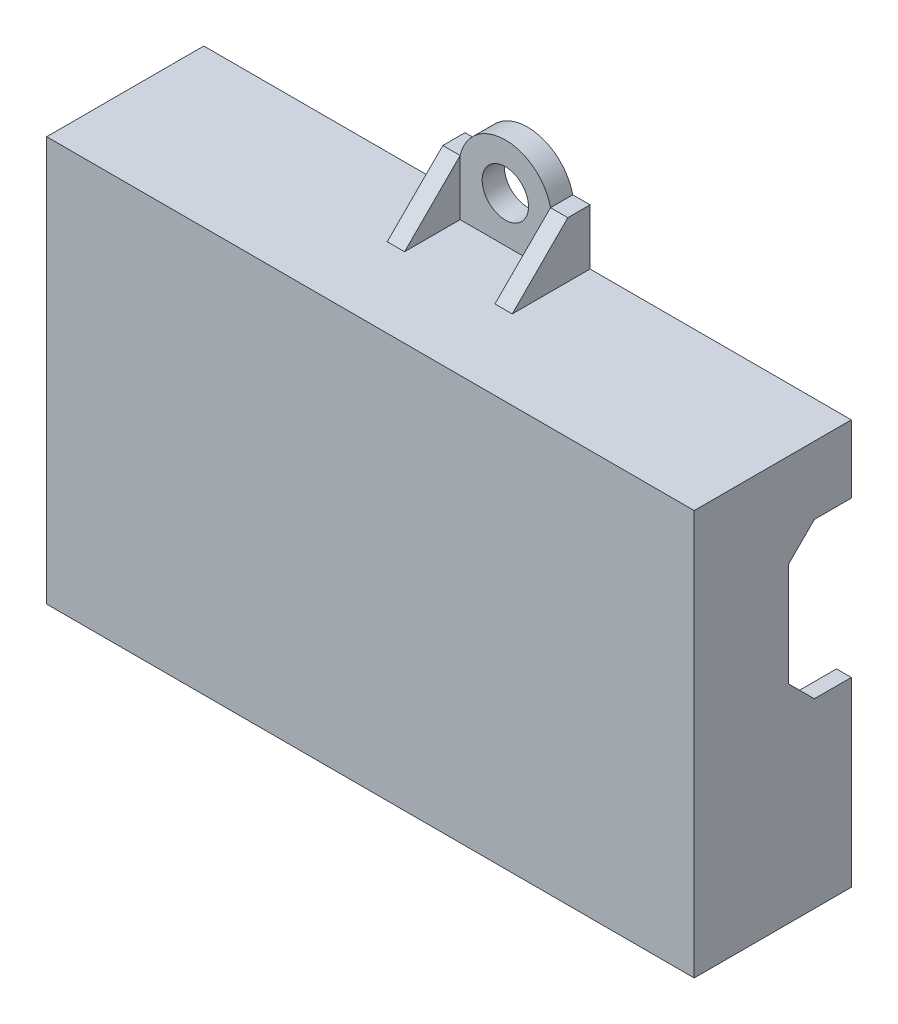
SolidWorks part; units mm, degrees
ref_plane "Front Plane" through (0, 0, 0) normal (0, 0, 1) x (1, 0, 0)
ref_plane "Top Plane" through (0, 0, 0) normal (0, 1, 0) x (1, 0, 0)
ref_plane "Right Plane" through (0, 0, 0) normal (1, 0, 0) x (0, 0, -1)
sketch "Sketch1" plane through (0, 0, 0) normal (0, 0, 1) x (1, 0, 0)
  line L0 (-16.375, 9.825) -> (16.375, -9.825) construction
  line L1 (-16.375, -9.825) -> (-16.675, -9.825) construction
  line L2 (16.675, 10.125) -> (-16.675, 10.125)
  line L3 (16.675, 10.125) -> (16.675, -10.125)
  line L4 (-16.375, 9.825) -> (-16.375, -9.825)
  line L5 (-16.375, -9.825) -> (16.375, -9.825)
  line L6 (16.375, -9.825) -> (16.375, 9.825)
  line L7 (16.375, 9.825) -> (-16.375, 9.825)
  line L8 (-16.375, 9.825) -> (-16.375, -9.825)
  line L9 (-16.375, -9.825) -> (16.375, -9.825)
  line L10 (16.375, -9.825) -> (16.375, 9.825)
  line L11 (16.375, 9.825) -> (-16.375, 9.825)
  line L12 (16.675, -10.125) -> (-16.675, -10.125)
  line L13 (-16.675, 10.125) -> (-16.675, -10.125)
  line L14 (16.675, 10.125) -> (-16.675, -10.125) construction
  line L15 (-13.9701, -11.875) -> (-3.4641, -11.875)
  line L18 (3.4641, -11.875) -> (13.9701, -11.875)
  line L19 (14.8161, -12.3418) -> (24.6724, -27.981)
  line L20 (31.4404, -23.7156) -> (19.404, -4.6171)
  line L21 (19.25, -4.084) -> (19.25, 4.084)
  line L22 (19.404, 4.6171) -> (31.4404, 23.7156)
  line L23 (24.6724, 27.981) -> (14.8161, 12.3418)
  line L24 (13.9701, 11.875) -> (3.4641, 11.875)
  line L25 (-3.4641, 11.875) -> (-13.9701, 11.875)
  line L26 (-14.8161, 12.3418) -> (-24.6724, 27.981)
  line L27 (-31.4404, 23.7156) -> (-19.404, 4.6171)
  line L28 (-19.25, 4.084) -> (-19.25, 3.4641)
  line L29 (-19.25, -3.4641) -> (-19.25, -4.084)
  line L30 (-19.404, -4.6171) -> (-31.4404, -23.7156)
  line L31 (-24.6724, -27.981) -> (-14.8161, -12.3418)
  line L32 (-13.9701, -11.875) -> (-3.4641, -11.875)
  line L33 (3.4641, -11.875) -> (13.9701, -11.875)
  line L34 (14.8161, -12.3418) -> (24.6724, -27.981)
  line L35 (31.4404, -23.7156) -> (19.404, -4.6171)
  line L36 (19.25, -4.084) -> (19.25, 4.084)
  line L37 (19.404, 4.6171) -> (31.4404, 23.7156)
  line L38 (24.6724, 27.981) -> (14.8161, 12.3418)
  line L39 (13.9701, 11.875) -> (3.4641, 11.875)
  line L40 (-3.4641, 11.875) -> (-13.9701, 11.875)
  line L41 (-14.8161, 12.3418) -> (-24.6724, 27.981)
  line L42 (-31.4404, 23.7156) -> (-19.404, 4.6171)
  line L43 (-19.25, 4.084) -> (-19.25, 3.4641)
  line L44 (-19.25, -3.4641) -> (-19.25, -4.084)
  line L45 (-19.404, -4.6171) -> (-31.4404, -23.7156)
  line L46 (-24.6724, -27.981) -> (-14.8161, -12.3418)
  line L47 (16.675, -10.125) -> (-16.675, 10.125) construction
  line L48 (-16.375, -9.825) -> (-16.375, -10.125) construction
  line L49 (-16.675, -10.125) -> (-17.475, -10.125) construction
  line L50 (17.475, 10.925) -> (-17.475, 10.925)
  line L51 (17.475, 10.925) -> (17.475, -10.925)
  line L52 (17.475, -10.925) -> (-17.475, -10.925)
  line L53 (-17.475, 10.925) -> (-17.475, -10.925)
  line L54 (17.475, 10.925) -> (-17.475, -10.925) construction
  line L55 (17.475, -10.925) -> (-17.475, 10.925) construction
  line L56 (-16.675, -10.125) -> (-16.675, -10.925) construction
  line L57 (-20.3929, -2.4744) -> (-17.475, -2.4744)
  line L58 (-20.3929, 2.4744) -> (-17.475, 2.4744)
  line L59 (-2.4744, -13.0179) -> (-2.4744, -10.925)
  line L60 (2.4744, -13.0179) -> (2.4744, -10.925)
  line L61 (-2.4744, 13.0179) -> (-2.4744, 10.925)
  line L62 (2.4744, 13.0179) -> (2.4744, 10.925)
  circle A0 centre (0, -13.375) radius 1.25
  circle A1 centre (-20.75, 0) radius 1.25
  circle A2 centre (0, 13.375) radius 1.25
  arc A32 (-2.4744, -13.0179) -> (-3.4641, -11.875) centre (-3.4641, -12.875) ccw
  arc A33 (-2.4744, -13.0179) -> (2.4744, -13.0179) centre (0, -13.375) ccw
  arc A34 (3.4641, -11.875) -> (2.4744, -13.0179) centre (3.4641, -12.875) ccw
  arc A35 (14.8161, -12.3418) -> (13.9701, -11.875) centre (13.9701, -12.875) ccw
  arc A36 (24.7505, -28.8963) -> (24.6724, -27.981) centre (23.8264, -28.5142) ccw
  arc A37 (24.7505, -28.8963) -> (32.2325, -24.1809) centre (31.8198, -31.8198) ccw
  arc A38 (31.4404, -23.7156) -> (32.2325, -24.1809) centre (32.2864, -23.1824) ccw
  arc A39 (19.25, -4.084) -> (19.404, -4.6171) centre (20.25, -4.084) ccw
  arc A40 (19.404, 4.6171) -> (19.25, 4.084) centre (20.25, 4.084) ccw
  arc A41 (32.2325, 24.1809) -> (31.4404, 23.7156) centre (32.2864, 23.1824) ccw
  arc A42 (32.2325, 24.1809) -> (24.7505, 28.8963) centre (31.8198, 31.8198) ccw
  arc A43 (24.6724, 27.981) -> (24.7505, 28.8963) centre (23.8264, 28.5142) ccw
  arc A44 (13.9701, 11.875) -> (14.8161, 12.3418) centre (13.9701, 12.875) ccw
  arc A45 (2.4744, 13.0179) -> (3.4641, 11.875) centre (3.4641, 12.875) ccw
  arc A46 (2.4744, 13.0179) -> (-2.4744, 13.0179) centre (0, 13.375) ccw
  arc A47 (-3.4641, 11.875) -> (-2.4744, 13.0179) centre (-3.4641, 12.875) ccw
  arc A48 (-14.8161, 12.3418) -> (-13.9701, 11.875) centre (-13.9701, 12.875) ccw
  arc A49 (-24.7505, 28.8963) -> (-24.6724, 27.981) centre (-23.8264, 28.5142) ccw
  arc A50 (-24.7505, 28.8963) -> (-32.2325, 24.1809) centre (-31.8198, 31.8198) ccw
  arc A51 (-31.4404, 23.7156) -> (-32.2325, 24.1809) centre (-32.2864, 23.1824) ccw
  arc A52 (-19.25, 4.084) -> (-19.404, 4.6171) centre (-20.25, 4.084) ccw
  arc A53 (-20.3929, 2.4744) -> (-19.25, 3.4641) centre (-20.25, 3.4641) ccw
  arc A54 (-20.3929, 2.4744) -> (-20.3929, -2.4744) centre (-20.75, 0) ccw
  arc A55 (-19.25, -3.4641) -> (-20.3929, -2.4744) centre (-20.25, -3.4641) ccw
  arc A56 (-19.404, -4.6171) -> (-19.25, -4.084) centre (-20.25, -4.084) ccw
  arc A57 (-32.2325, -24.1809) -> (-31.4404, -23.7156) centre (-32.2864, -23.1824) ccw
  arc A58 (-32.2325, -24.1809) -> (-24.7505, -28.8963) centre (-31.8198, -31.8198) ccw
  arc A59 (-24.6724, -27.981) -> (-24.7505, -28.8963) centre (-23.8264, -28.5142) ccw
  arc A60 (-13.9701, -11.875) -> (-14.8161, -12.3418) centre (-13.9701, -12.875) ccw
  arc A61 (-2.4744, -13.0179) -> (-3.4641, -11.875) centre (-3.4641, -12.875) ccw
  arc A62 (-2.4744, -13.0179) -> (2.4744, -13.0179) centre (0, -13.375) ccw
  arc A63 (3.4641, -11.875) -> (2.4744, -13.0179) centre (3.4641, -12.875) ccw
  arc A64 (14.8161, -12.3418) -> (13.9701, -11.875) centre (13.9701, -12.875) ccw
  arc A65 (24.7505, -28.8963) -> (24.6724, -27.981) centre (23.8264, -28.5142) ccw
  arc A66 (24.7505, -28.8963) -> (32.2325, -24.1809) centre (31.8198, -31.8198) ccw
  arc A67 (31.4404, -23.7156) -> (32.2325, -24.1809) centre (32.2864, -23.1824) ccw
  arc A68 (19.25, -4.084) -> (19.404, -4.6171) centre (20.25, -4.084) ccw
  arc A69 (19.404, 4.6171) -> (19.25, 4.084) centre (20.25, 4.084) ccw
  arc A70 (32.2325, 24.1809) -> (31.4404, 23.7156) centre (32.2864, 23.1824) ccw
  arc A71 (32.2325, 24.1809) -> (24.7505, 28.8963) centre (31.8198, 31.8198) ccw
  arc A72 (24.6724, 27.981) -> (24.7505, 28.8963) centre (23.8264, 28.5142) ccw
  arc A73 (13.9701, 11.875) -> (14.8161, 12.3418) centre (13.9701, 12.875) ccw
  arc A74 (2.4744, 13.0179) -> (3.4641, 11.875) centre (3.4641, 12.875) ccw
  arc A75 (2.4744, 13.0179) -> (-2.4744, 13.0179) centre (0, 13.375) ccw
  arc A76 (-3.4641, 11.875) -> (-2.4744, 13.0179) centre (-3.4641, 12.875) ccw
  arc A77 (-14.8161, 12.3418) -> (-13.9701, 11.875) centre (-13.9701, 12.875) ccw
  arc A78 (-24.7505, 28.8963) -> (-24.6724, 27.981) centre (-23.8264, 28.5142) ccw
  arc A79 (-24.7505, 28.8963) -> (-32.2325, 24.1809) centre (-31.8198, 31.8198) ccw
  arc A80 (-31.4404, 23.7156) -> (-32.2325, 24.1809) centre (-32.2864, 23.1824) ccw
  arc A81 (-19.25, 4.084) -> (-19.404, 4.6171) centre (-20.25, 4.084) ccw
  arc A82 (-20.3929, 2.4744) -> (-19.25, 3.4641) centre (-20.25, 3.4641) ccw
  arc A83 (-20.3929, 2.4744) -> (-20.3929, -2.4744) centre (-20.75, 0) ccw
  arc A84 (-19.25, -3.4641) -> (-20.3929, -2.4744) centre (-20.25, -3.4641) ccw
  arc A85 (-19.404, -4.6171) -> (-19.25, -4.084) centre (-20.25, -4.084) ccw
  arc A86 (-32.2325, -24.1809) -> (-31.4404, -23.7156) centre (-32.2864, -23.1824) ccw
  arc A87 (-32.2325, -24.1809) -> (-24.7505, -28.8963) centre (-31.8198, -31.8198) ccw
  arc A88 (-24.6724, -27.981) -> (-24.7505, -28.8963) centre (-23.8264, -28.5142) ccw
  arc A89 (-13.9701, -11.875) -> (-14.8161, -12.3418) centre (-13.9701, -12.875) ccw
  point P6 (0, 0)
  point P25 (0, 0)
  dimension "D4" = 0.8
  dimension "D5" = 2.5
  dimension "D1" = 0
  dimension "D2" = 0
  dimension "D3" = 0.3
extrude "Boss-Extrude1" add sketch "Sketch1" along normal offset from surface (7.98 mm away) 2.5 contours A84 L57 L53 L58 A82 A83 | L50 L53 L52 L51 L13 L2 L3 L12 | A63 L60 L52 L59 A61 A62 | A76 L61 L50 L62 A74 A75 region at (-2.404, -11.8286, 0) region at (-9.9747, -10.5128, 0) region at (-18.7911, -2.398, 0) region at (0, 10.9954, 0) offset beyond the face yes
sketch "Sketch2" plane through (0, 0, 7.98) normal (0, 0, 1) x (1, 0, 0)
  line L0 (-2.5, 10.925) -> (2.4744, 10.925)
  line L1 (-17.475, 2.4744) -> (-17.475, -2.5)
  line L2 (-2.5, -10.925) -> (2.4744, -10.925)
  line L6 (-20.1071, -2.4744) -> (-17.475, -2.4744)
  line L7 (-20.1071, -2.4744) -> (-17.475, -2.4744)
  line L8 (-17.475, -2.4744) -> (-17.475, -10.925)
  line L9 (-17.475, -2.4744) -> (-17.475, -10.925)
  line L20 (-17.475, -10.925) -> (-2.4744, -10.925)
  line L21 (-17.475, -10.925) -> (-2.4744, -10.925)
  line L22 (-2.4744, -10.925) -> (-2.4744, -12.7321)
  line L23 (-2.4744, -10.925) -> (-2.4744, -12.7321)
  line L24 (2.4744, -12.7321) -> (2.4744, -10.925)
  line L25 (2.4744, -12.7321) -> (2.4744, -10.925)
  line L26 (2.4744, -10.925) -> (17.475, -10.925)
  line L27 (2.4744, -10.925) -> (17.475, -10.925)
  line L28 (17.475, -10.925) -> (17.475, 10.925)
  line L29 (17.475, -10.925) -> (17.475, 10.925)
  line L30 (17.475, 10.925) -> (2.4744, 10.925)
  line L31 (17.475, 10.925) -> (2.4744, 10.925)
  line L32 (2.4744, 10.925) -> (2.4744, 12.7321)
  line L33 (2.4744, 10.925) -> (2.4744, 12.7321)
  line L34 (-2.4744, 12.7321) -> (-2.4744, 10.925)
  line L35 (-2.4744, 12.7321) -> (-2.4744, 10.925)
  line L36 (-2.4744, 10.925) -> (-17.475, 10.925)
  line L37 (-2.4744, 10.925) -> (-17.475, 10.925)
  line L38 (-17.475, 10.925) -> (-17.475, 2.4744)
  line L39 (-17.475, 10.925) -> (-17.475, 2.4744)
  line L40 (-17.475, 2.4744) -> (-20.1071, 2.4744)
  line L41 (-17.475, 2.4744) -> (-20.1071, 2.4744)
  arc A9 (-20.1071, -2.4744) -> (-20.3929, -2.4744) centre (-20.25, -3.4641) ccw
  arc A10 (-20.1071, -2.4744) -> (-20.3929, -2.4744) centre (-20.25, -3.4641) ccw
  arc A11 (-2.4744, -13.0179) -> (-2.4744, -12.7321) centre (-3.4641, -12.875) ccw
  arc A12 (-2.4744, -13.0179) -> (-2.4744, -12.7321) centre (-3.4641, -12.875) ccw
  arc A13 (-2.4744, -13.0179) -> (2.4744, -13.0179) centre (0, -13.375) ccw
  arc A14 (-2.4744, -13.0179) -> (2.4744, -13.0179) centre (0, -13.375) ccw
  arc A15 (2.4744, -12.7321) -> (2.4744, -13.0179) centre (3.4641, -12.875) ccw
  arc A16 (2.4744, -12.7321) -> (2.4744, -13.0179) centre (3.4641, -12.875) ccw
  arc A17 (2.4744, 13.0179) -> (2.4744, 12.7321) centre (3.4641, 12.875) ccw
  arc A18 (2.4744, 13.0179) -> (2.4744, 12.7321) centre (3.4641, 12.875) ccw
  arc A19 (2.4744, 13.0179) -> (-2.4744, 13.0179) centre (0, 13.375) ccw
  arc A20 (2.4744, 13.0179) -> (-2.4744, 13.0179) centre (0, 13.375) ccw
  arc A21 (-2.4744, 12.7321) -> (-2.4744, 13.0179) centre (-3.4641, 12.875) ccw
  arc A22 (-2.4744, 12.7321) -> (-2.4744, 13.0179) centre (-3.4641, 12.875) ccw
  arc A23 (-20.3929, 2.4744) -> (-20.1071, 2.4744) centre (-20.25, 3.4641) ccw
  arc A24 (-20.3929, 2.4744) -> (-20.1071, 2.4744) centre (-20.25, 3.4641) ccw
  arc A25 (-20.3929, 2.4744) -> (-20.3929, -2.4744) centre (-20.75, 0) ccw
  arc A26 (-20.3929, 2.4744) -> (-20.3929, -2.4744) centre (-20.75, 0) ccw
  dimension "D1" = 0
extrude "Cut-Extrude1" cut sketch "Sketch2" against normal offset from surface (6.78 mm away) 1.2 contours L0 | L1 | L2 region at (0, 13.1729, 7.98) region at (-20.1307, 0, 7.98) region at (0, -13.1729, 7.98) up to face at (-5.4003, 0, 0)
sketch "Sketch3" plane through (17.475, 0, 0) normal (1, 0, 0) x (0, 0, -1)
  line L0 (0, 10.925) -> (0, -10.925) construction
  line L1 (0, 7.265) -> (-3.395, 7.265)
  line L2 (0, 7.265) -> (0, -1.115)
  line L3 (0, -1.115) -> (-3.395, -1.115)
  line L4 (-3.395, 7.265) -> (-3.395, -1.115)
  line L6 (-1.3, 7.065) -> (-1.3, 7.265) construction
  line L7 (-1.3, -0.915) -> (-1.3, -1.115) construction
  line L8 (-3.195, 5.375) -> (-3.395, 5.375) construction
  dimension "D1" = 0.2
extrude "Cut-Extrude2" cut sketch "Sketch3" against normal up to next
chamfer "Chamfer1" distance 1.4 angle 45 2 edges at (17.075, -1.115, 3.395) (17.075, 7.265, 3.395)
sketch "Sketch4" plane through (0, 0, 7.98) normal (0, 0, 1) x (1, 0, 0)
  line L4 (-17.475, 10.925) -> (-17.475, -10.925)
  line L8 (-17.475, 10.925) -> (-17.475, -10.925)
  line L17 (-17.475, -10.925) -> (17.475, -10.925)
  line L18 (-17.475, -10.925) -> (17.475, -10.925)
  line L25 (17.475, -10.925) -> (17.475, 10.925)
  line L26 (17.475, -10.925) -> (17.475, 10.925)
  line L27 (17.475, 10.925) -> (-17.475, 10.925)
  line L28 (17.475, 10.925) -> (-17.475, 10.925)
  dimension "D1" = 0
extrude "Boss-Extrude2" add sketch "Sketch4" along normal blind 0.5
sketch "Sketch8" plane through (-17.475, 0, 0) normal (-1, 0, 0) x (0, 0, 1)
  line L1 (5.93, 3.385) -> (7.98, 3.385)
  line L2 (5.93, 3.385) -> (5.93, -3.385)
  line L3 (5.93, -3.385) -> (7.98, -3.385)
  line L4 (7.98, 3.385) -> (7.98, -3.385)
  line L7 (7.08, 3.385) -> (5.93, 3.385) construction
  line L8 (5.93, -3.385) -> (7.08, -3.385) construction
  line L9 (5.93, 3.385) -> (5.93, 2.4) construction
  line L10 (7.98, -3.985) -> (7.98, -2.4) construction
extrude "Cut-Extrude3" cut sketch "Sketch8" against normal up to next
sketch "Sketch9" plane through (0, 0, 7.98) normal (0, 0, -1) x (-1, 0, 0)
  line L1 (16.875, 2.4) -> (17.475, 2.4)
  line L2 (16.875, 2.4) -> (16.875, 3.385)
  line L3 (16.875, 3.385) -> (17.475, 3.385)
  line L4 (17.475, 2.4) -> (17.475, 3.385)
  line L5 (16.875, -2.4) -> (17.475, -2.4)
  line L6 (16.875, -2.4) -> (16.875, -3.385)
  line L7 (16.875, -3.385) -> (17.475, -3.385)
  line L8 (17.475, -2.4) -> (17.475, -3.385)
extrude "Boss-Extrude6" add sketch "Sketch9" along normal blind 0.8
sketch "Sketch11" plane through (0, 0, 7.98) normal (0, 0, -1) x (-1, 0, 0)
  line L24 (16.975, -4.085) -> (16.975, -2.3)
  line L25 (16.975, -2.3) -> (15.685, -2.3)
  line L26 (15.685, -2.3) -> (15.685, 2.3)
  line L27 (15.685, 2.3) -> (16.975, 2.3)
  line L28 (16.975, 2.3) -> (16.975, 4.085)
  line L29 (16.975, 4.085) -> (10.555, 4.085)
  line L30 (10.555, 4.085) -> (10.555, 2.4)
  line L31 (10.555, 2.4) -> (5.955, 2.4)
  line L32 (5.955, 2.4) -> (5.955, -2.4)
  line L33 (5.955, -2.4) -> (10.555, -2.4)
  line L34 (10.555, -2.4) -> (10.555, -4.085)
  line L35 (10.555, -4.085) -> (16.975, -4.085)
  line L36 (16.975, -4.085) -> (16.975, -2.3)
  line L37 (16.975, -2.3) -> (15.685, -2.3)
  line L38 (15.685, -2.3) -> (15.685, 2.3)
  line L39 (15.685, 2.3) -> (16.975, 2.3)
  line L40 (16.975, 2.3) -> (16.975, 4.085)
  line L41 (16.975, 4.085) -> (10.555, 4.085)
  line L42 (10.555, 4.085) -> (10.555, 2.4)
  line L43 (10.555, 2.4) -> (5.955, 2.4)
  line L44 (5.955, 2.4) -> (5.955, -2.4)
  line L45 (5.955, -2.4) -> (10.555, -2.4)
  line L46 (10.555, -2.4) -> (10.555, -4.085)
  line L47 (10.555, -4.085) -> (16.975, -4.085)
  line L48 (5.955, 1.9) -> (3.955, 1.9)
  line L49 (3.955, 0) -> (17.685, 0) construction
  line L50 (5.955, -1.9) -> (3.955, -1.9)
  line L51 (16.675, 6.085) -> (16.675, 4.085)
  line L53 (16.675, 10.125) -> (16.675, 3.385) construction
  line L54 (16.675, -6.085) -> (16.675, -4.085)
  line L55 (16.675, -3.385) -> (16.675, -10.125) construction
  line L60 (18.975, -6.085) -> (18.975, -0.3)
  line L61 (18.975, -0.3) -> (17.685, -0.3)
  line L62 (17.685, -0.3) -> (17.685, 0.3)
  line L63 (17.685, 0.3) -> (18.975, 0.3)
  line L64 (18.975, 0.3) -> (18.975, 6.085)
  line L65 (18.975, 6.085) -> (8.555, 6.085)
  line L66 (8.555, 6.085) -> (8.555, 4.4)
  line L67 (8.555, 4.4) -> (3.955, 4.4)
  line L68 (3.955, 4.4) -> (3.955, -4.4)
  line L69 (3.955, -4.4) -> (8.555, -4.4)
  line L70 (8.555, -4.4) -> (8.555, -6.085)
  line L71 (8.555, -6.085) -> (18.975, -6.085)
  line L72 (18.975, -6.085) -> (18.975, -0.3)
  line L73 (18.975, -0.3) -> (17.685, -0.3)
  line L74 (17.685, -0.3) -> (17.685, 0.3)
  line L75 (17.685, 0.3) -> (18.975, 0.3)
  line L76 (18.975, 0.3) -> (18.975, 6.085)
  line L77 (18.975, 6.085) -> (8.555, 6.085)
  line L78 (8.555, 6.085) -> (8.555, 4.4)
  line L79 (8.555, 4.4) -> (3.955, 4.4)
  line L80 (3.955, 4.4) -> (3.955, -4.4)
  line L81 (3.955, -4.4) -> (8.555, -4.4)
  line L82 (8.555, -4.4) -> (8.555, -6.085)
  line L83 (8.555, -6.085) -> (18.975, -6.085)
  line M27 (16.675, -10.125) -> (16.675, -3.385)
  line M31 (16.675, 3.385) -> (16.675, 10.125)
  dimension "D3" = 0.5
  dimension "D1" = 0.1
  dimension "D2" = 2.1
extrude "Boss-Extrude7" add sketch "Sketch11" along normal blind 2.5 contours L79 L80 L48 L44 L43 L42 L41 L77 L78 M31 | L82 L83 L47 L46 L45 L44 L50 L80 L81 M27 region at (-10.0493, -4.2582, 7.98) region at (-10.0493, 4.2582, 7.98)
sketch "Sketch12" plane through (0, 0, 7.98) normal (0, 0, -1) x (-1, 0, 0)
  line L0 (16.675, -6.085) -> (16.675, -10.125) construction
  line L1 (-3.0335, 0) -> (1.6631, 0) construction
  line L2 (16.675, 8.105) -> (14.655, 8.105)
  line L3 (16.675, 8.105) -> (16.675, 6.085)
  line L4 (16.675, 6.085) -> (14.655, 6.085)
  line L5 (16.675, -8.105) -> (14.655, -8.105)
  line L6 (16.675, -8.105) -> (16.675, -6.085)
  line L7 (16.675, -6.085) -> (14.655, -6.085)
  line L8 (14.655, -8.105) -> (14.655, -6.085)
  line L9 (8.555, -6.085) -> (16.675, -6.085) construction
  line L10 (14.655, 8.105) -> (14.655, 6.085)
  line L11 (-16.675, 10.125) -> (-16.675, -10.125) construction
  line L12 (-14.655, 2) -> (-16.675, 2)
  line L13 (-14.655, 2) -> (-14.655, -2)
  line L14 (-14.655, -2) -> (-16.675, -2)
  line L15 (-16.675, 2) -> (-16.675, -2)
  line L16 (-14.655, 2) -> (-16.675, -2) construction
  line L17 (-14.655, -2) -> (-16.675, 2) construction
  point P16 (-15.665, 0)
  dimension "D1" = 4
extrude "Boss-Extrude8" add sketch "Sketch12" along normal up to surface (3.95 mm away)
sketch "Sketch13" plane through (-17.475, 0, 0) normal (-1, 0, 0) x (0, 0, 1)
  line L0 (7.18, 2.4) -> (7.18, 3.385) construction
  line L1 (7.98, 2.4) -> (7.18, 2.4)
  line L2 (7.98, 2.4) -> (7.98, 2.9)
  line L3 (7.98, 2.9) -> (7.18, 2.9)
  line L4 (7.18, 2.4) -> (7.18, 2.9)
  line L5 (5.93, 0) -> (7.98, 0) construction
  line L6 (7.18, 3.385) -> (5.43, 3.385)
  line L7 (7.18, 3.385) -> (7.18, 3.885)
  line L8 (7.18, 3.885) -> (5.43, 3.885)
  line L9 (5.43, 3.385) -> (5.43, 3.885)
  line L10 (5.93, 3.385) -> (5.93, -3.385) construction
  line L11 (7.98, -2) -> (7.98, 2) construction
  line L12 (5.43, 1.6925) -> (5.93, 1.6925) construction
  line L13 (5.43, 3.385) -> (5.93, 3.385)
  line L14 (5.43, 3.385) -> (5.43, -3.385)
  line L15 (5.93, 0) -> (5.93, -3.385)
  line L16 (5.93, 3.385) -> (5.93, 0)
  line L17 (7.98, -2.4) -> (7.98, -2.9)
  line L18 (7.98, -2.9) -> (7.18, -2.9)
  line L19 (7.18, -3.385) -> (7.18, -3.885)
  line L20 (7.18, -3.885) -> (5.43, -3.885)
  line L21 (5.43, -3.385) -> (5.43, -3.885)
  line L22 (5.43, 3.385) -> (5.43, -3.385)
  line L23 (1.2, -2.5) -> (1.2, 2.5) construction
  line L24 (0, 3.3744) -> (1.2, 3.3744)
  line L25 (0, 3.3744) -> (0, 5.8744)
  line L26 (0, 5.8744) -> (1.2, 5.8744)
  line L27 (1.2, 3.3744) -> (1.2, 5.8744)
  line L28 (1.2, 2.4744) -> (0, 2.4744) construction
  line L29 (0, 10.925) -> (0, 2.4744) construction
  line M12 (7.98, -2.4) -> (7.18, -2.4)
  line M13 (7.18, -2.4) -> (7.18, -3.385)
  line M14 (7.18, -3.385) -> (5.93, -3.385)
  line M15 (5.93, -3.385) -> (5.93, 3.385)
  line M16 (5.93, 3.385) -> (7.18, 3.385)
  line M17 (7.18, 3.385) -> (7.18, 2.4)
  line M18 (7.18, 2.4) -> (7.98, 2.4)
  line M22 (0, 10.925) -> (0, 2.4744)
  dimension "D1" = 0.5
  dimension "D2" = 2.5
  dimension "D3" = 0.9
extrude "Cut-Extrude4" cut sketch "Sketch13" against normal up to next contours L9 L6 L7 L8 M16 | L2 L3 M17 M18 | L14 L21 L20 L19 L6 M14 M15 | L18 L17 M12 M13 | L24 L27 L26 M22 region at (-17.475, -2.65, 7.58) region at (-17.475, 3.635, 6.305) region at (-17.475, 2.65, 7.58) region at (-17.475, -0.7466, 5.8084) region at (-17.475, 4.6244, 0.6)
sketch "Sketch14" plane through (0, 0, 5.48) normal (0, 0, -1) x (-1, 0, 0)
  line L0 (16.675, 4.085) -> (10.555, 4.085) construction
  line L1 (16.675, 6.085) -> (14.275, 6.085)
  line L2 (16.675, 6.085) -> (16.675, 3.685)
  line L3 (16.675, 3.685) -> (14.275, 3.685)
  line L4 (14.275, 6.085) -> (14.275, 3.685)
  line L5 (3.955, 1.9) -> (3.955, -1.9) construction
  line L6 (3.955, 0) -> (16.675, 0) construction
  line L8 (16.675, -6.085) -> (16.675, -3.685)
  line L9 (16.675, -6.085) -> (14.275, -6.085)
  line L10 (14.275, -6.085) -> (14.275, -3.685)
  line L11 (16.675, -3.685) -> (14.275, -3.685)
  line L12 (5.955, 2.4) -> (5.955, 1.9) construction
  line L13 (3.955, 4.4) -> (5.955, 4.4)
  line L14 (3.955, 4.4) -> (3.955, 1.5)
  line L15 (3.955, 1.5) -> (5.955, 1.5)
  line L16 (5.955, 4.4) -> (5.955, 1.5)
  line L17 (15.475, 3.685) -> (15.475, 4.085) construction
  line L18 (16.675, 4.085) -> (10.555, 4.085) construction
  line L19 (4.955, 1.5) -> (4.955, 1.9) construction
  line L20 (5.955, 1.9) -> (3.955, 1.9) construction
  line L21 (3.955, -4.4) -> (5.955, -4.4)
  line L22 (5.955, -4.4) -> (5.955, -1.5)
  line L23 (3.955, -1.5) -> (5.955, -1.5)
  line L24 (3.955, -4.4) -> (3.955, -1.5)
  line L25 (16.675, 3.3744) -> (16.675, -10.125) construction
  dimension "D1" = 0.4
extrude "Boss-Extrude9" add sketch "Sketch14" along normal blind 0.6
ref_plane "Plane1" through (0, 0, 2.95) normal (0, 0, -1) x (-1, 0, 0)
sketch "Sketch16" plane through (0, 0, 2.95) normal (0, 0, -1) x (-1, 0, 0)
  line L0 (-16.675, 10.125) -> (16.675, 10.125) construction
  line L1 (6.175, 10.125) -> (8.675, 10.125)
  line L2 (6.175, 10.125) -> (6.175, 9.425)
  line L3 (6.175, 9.425) -> (8.675, 9.425)
  line L4 (8.675, 10.125) -> (8.675, 9.425)
  line L6 (16.675, 10.125) -> (16.675, 5.8744) construction
  line L8 (-16.675, 10.125) -> (-14.175, 10.125)
  line L9 (-16.675, 10.125) -> (-16.675, 9.425)
  line L10 (-16.675, 9.425) -> (-14.175, 9.425)
  line L11 (-14.175, 10.125) -> (-14.175, 9.425)
  line L12 (16.675, -10.125) -> (14.175, -10.125)
  line L13 (16.675, -10.125) -> (16.675, -9.425)
  line L14 (16.675, -9.425) -> (14.175, -9.425)
  line L15 (14.175, -10.125) -> (14.175, -9.425)
  line L16 (-16.675, -10.125) -> (-14.175, -10.125)
  line L17 (-16.675, -10.125) -> (-16.675, -9.425)
  line L18 (-16.675, -9.425) -> (-14.175, -9.425)
  line L19 (-14.175, -10.125) -> (-14.175, -9.425)
  dimension "D1" = 2.5
  dimension "D2" = 0.7
  dimension "D3" = 8
extrude "Boss-Extrude13" add sketch "Sketch16" along normal blind 0.8
chamfer "Chamfer2" distance 1 angle 45 2 edges at (-10.555, 3.2425, 5.48) (-10.555, -3.2425, 5.48)
sketch "Sketch17" plane through (0, 0, 1.2) normal (0, 0, 1) x (1, 0, 0)
  line L0 (-23.25, 0) -> (-17.475, 0) construction
  line L1 (-17.475, 10.925) -> (-17.475, -10.925) construction
  line L2 (0, 15.875) -> (0, -15.875) construction
  line L3 (-20.1071, 2.4744) -> (-17.475, 2.4744) construction
  line L4 (-20.475, -3.3744) -> (-17.475, -3.3744)
  line L5 (-20.475, -3.3744) -> (-20.475, 3.3744)
  line L6 (-20.475, 3.3744) -> (-17.475, 3.3744)
  line L7 (-17.475, -3.3744) -> (-17.475, 3.3744)
  line L8 (-20.475, -3.3744) -> (-17.475, 3.3744) construction
  line L9 (-20.475, 3.3744) -> (-17.475, -3.3744) construction
  line L10 (17.475, 10.925) -> (-17.475, 10.925) construction
  line L11 (-3.3744, 10.925) -> (3.3744, 10.925)
  line L12 (-3.3744, 10.925) -> (-3.3744, 13.925)
  line L13 (-20.1071, -2.4744) -> (-17.475, -2.4744)
  line L14 (-17.475, -2.4744) -> (-17.475, 2.4744)
  line L15 (-17.475, 2.4744) -> (-20.1071, 2.4744)
  line L16 (-20.1071, -2.4744) -> (-17.475, -2.4744)
  line L17 (-17.475, -2.4744) -> (-17.475, 2.4744)
  line L18 (-17.475, 2.4744) -> (-20.1071, 2.4744)
  line L22 (-2.4744, 12.7321) -> (-2.4744, 10.525)
  line L23 (-2.4744, 10.525) -> (2.4744, 10.525)
  line L24 (2.4744, 10.525) -> (2.4744, 12.7321)
  line L28 (2.4744, -12.7321) -> (2.4744, -10.525)
  line L29 (2.4744, -10.525) -> (-2.4744, -10.525)
  line L30 (-2.4744, -10.525) -> (-2.4744, -12.7321)
  line L31 (-3.3744, 13.925) -> (3.3744, 13.925)
  line L32 (3.3744, 10.925) -> (3.3744, 13.925)
  line L33 (-3.3744, 10.925) -> (3.3744, 13.925) construction
  line L34 (-3.3744, 13.925) -> (3.3744, 10.925) construction
  line L35 (-17.475, -10.925) -> (17.475, -10.925) construction
  line L36 (3.3744, -13.925) -> (-3.3744, -13.925)
  line L37 (3.3744, -13.925) -> (3.3744, -10.925)
  line L38 (3.3744, -10.925) -> (-3.3744, -10.925)
  line L39 (-3.3744, -13.925) -> (-3.3744, -10.925)
  line L40 (3.3744, -13.925) -> (-3.3744, -10.925) construction
  line L41 (3.3744, -10.925) -> (-3.3744, -13.925) construction
  arc A0 (-20.3929, 2.4744) -> (-20.3929, -2.4744) centre (-20.75, 0) ccw construction
  arc A1 (2.4744, 13.0179) -> (-2.4744, 13.0179) centre (0, 13.375) ccw construction
  arc A2 (-2.4744, -13.0179) -> (2.4744, -13.0179) centre (0, -13.375) ccw construction
  arc A6 (-20.3929, 2.4744) -> (-20.1071, 2.4744) centre (-20.25, 3.4641) ccw
  arc A7 (-20.3929, 2.4744) -> (-20.3929, -2.4744) centre (-20.75, 0) ccw
  arc A8 (-20.1071, -2.4744) -> (-20.3929, -2.4744) centre (-20.25, -3.4641) ccw
  arc A9 (-20.3929, 2.4744) -> (-20.1071, 2.4744) centre (-20.25, 3.4641) ccw
  arc A10 (-20.3929, 2.4744) -> (-20.3929, -2.4744) centre (-20.75, 0) ccw
  arc A11 (-20.1071, -2.4744) -> (-20.3929, -2.4744) centre (-20.25, -3.4641) ccw
  arc A15 (2.4744, 13.0179) -> (2.4744, 12.7321) centre (3.4641, 12.875) ccw
  arc A16 (2.4744, 13.0179) -> (-2.4744, 13.0179) centre (0, 13.375) ccw
  arc A17 (-2.4744, 12.7321) -> (-2.4744, 13.0179) centre (-3.4641, 12.875) ccw
  arc A21 (-2.4744, -13.0179) -> (-2.4744, -12.7321) centre (-3.4641, -12.875) ccw
  arc A22 (-2.4744, -13.0179) -> (2.4744, -13.0179) centre (0, -13.375) ccw
  arc A23 (2.4744, -12.7321) -> (2.4744, -13.0179) centre (3.4641, -12.875) ccw
  point P15 (-18.975, 0)
  point P38 (0, 12.425)
  point P57 (0, -12.425)
  line M26 (2.4744, -12.7321) -> (2.4744, -10.925)
  line M28 (-2.4744, -10.925) -> (-2.4744, -12.7321)
  arc M29 (-2.4744, -12.7321) -> (-2.4744, -13.0179) centre (-3.4641, -12.875) cw
  arc M30 (-2.4744, -13.0179) -> (2.4744, -13.0179) centre (0, -13.375) ccw
  arc M31 (2.4744, -13.0179) -> (2.4744, -12.7321) centre (3.4641, -12.875) cw
  dimension "D1" = 0.9
  dimension "D2" = 3
  dimension "D3" = 0
extrude "Boss-Extrude17" add sketch "Sketch17" against normal up to surface (1.2 mm away) contours L18 L7 L6 L5 | L16 L5 L4 L7 | L22 A17 A16 L31 L12 L11 | A16 A15 L24 L11 L32 L31 | L37 L38 L36 M26 M31 M30 | L39 L36 L38 M30 M29 M28 region at (-18.9757, -2.9241, 1.2) region at (-18.9757, 2.9241, 1.2) region at (-2.9255, 12.4227, 1.2) region at (2.9255, 12.4227, 1.2) region at (2.9255, -12.4227, 1.2) region at (-2.9255, -12.4227, 1.2) up to face at (1.25, 13.375, 0)
sketch "Sketch18" plane through (0, 0, 1.2) normal (0, 0, 1) x (1, 0, 0)
  line L0 (-17.475, -3.3744) -> (-17.475, 3.3744) construction
  line L1 (-20.475, 3.3744) -> (-17.475, 3.3744)
  line L2 (-20.475, 3.3744) -> (-20.475, 2.4848)
  line L3 (-20.475, 2.4848) -> (-17.475, 2.4848)
  line L4 (-17.475, 3.3744) -> (-17.475, 2.4848)
  line L5 (-17.475, 10.925) -> (-17.475, -10.925) construction
  line L6 (-20.475, -2.4848) -> (-17.475, -2.4848)
  line L7 (-20.475, -2.4848) -> (-20.475, -3.3744)
  line L8 (-20.475, -3.3744) -> (-17.475, -3.3744)
  line L9 (-17.475, -2.4848) -> (-17.475, -3.3744)
  line L10 (17.475, 10.925) -> (-17.475, 10.925) construction
  line L11 (-2.4387, -13.925) -> (-3.3744, -13.925)
  line L12 (-2.4387, -13.925) -> (-2.4387, -10.925)
  line L13 (-2.4387, -10.925) -> (-3.3744, -10.925)
  line L14 (-3.3744, -13.925) -> (-3.3744, -10.925)
  line L15 (2.4387, -13.925) -> (3.3744, -13.925)
  line L16 (2.4387, -13.925) -> (2.4387, -10.925)
  line L17 (2.4387, -10.925) -> (3.3744, -10.925)
  line L18 (3.3744, -13.925) -> (3.3744, -10.925)
  line L19 (-2.4387, 13.925) -> (-3.3744, 13.925)
  line L20 (-2.4387, 13.925) -> (-2.4387, 10.925)
  line L21 (-2.4387, 10.925) -> (-3.3744, 10.925)
  line L22 (-3.3744, 13.925) -> (-3.3744, 10.925)
  line L23 (-3.3744, 10.925) -> (-3.3744, 13.925) construction
  line L24 (-20.475, -3.3744) -> (-17.475, -3.3744) construction
  line L25 (2.4387, 13.925) -> (3.3744, 13.925)
  line L26 (2.4387, 13.925) -> (2.4387, 10.925)
  line L27 (2.4387, 10.925) -> (3.3744, 10.925)
  line L28 (3.3744, 13.925) -> (3.3744, 10.925)
  point P9 (-20.475, 2.4848)
  point P14 (0, 0)
  point P42 (-20.475, -2.4848)
extrude "Boss-Extrude18" add sketch "Sketch18" along normal blind 3
chamfer "Chamfer3" distance 3 angle 45 6 edges at (-2.9066, 13.925, 4.2) (2.9066, 13.925, 4.2) (2.9066, -13.925, 4.2) (-2.9066, -13.925, 4.2) (-20.475, -2.9296, 4.2) (-20.475, 2.9296, 4.2)
sketch "Sketch19" [suppressed] plane through (0, 0, 1.2) normal (0, 0, 1) x (1, 0, 0)
  line L0 (2.4592, -13.825) -> (2.4592, -10.825) construction
  line L1 (2.4592, -10.825) -> (-2.4592, -10.825) construction
  line L2 (-2.4592, -10.825) -> (-2.4592, -13.825) construction
  line L4 (-20.375, -2.4719) -> (-17.375, -2.4719) construction
  line L5 (-17.375, -2.4719) -> (-17.375, 2.4719) construction
  line L6 (-17.375, 2.4719) -> (-20.375, 2.4719) construction
  line L8 (-2.4592, 10.825) -> (2.4592, 10.825) construction
  line L9 (2.4592, 10.825) -> (2.4592, 13.825) construction
  line L10 (-2.4592, 13.825) -> (-2.4592, 10.825) construction
  line L11 (2.4592, -13.825) -> (2.4592, -10.825)
  line L12 (2.4592, -10.825) -> (-2.4592, -10.825)
  line L13 (-2.4592, -10.825) -> (-2.4592, -13.825)
  line L15 (-20.375, -2.4719) -> (-17.375, -2.4719)
  line L16 (-17.375, -2.4719) -> (-17.375, 2.4719)
  line L17 (-17.375, 2.4719) -> (-20.375, 2.4719)
  line L19 (-2.4592, 10.825) -> (2.4592, 10.825)
  line L20 (2.4592, 10.825) -> (2.4592, 13.825)
  line L21 (-2.4592, 13.825) -> (-2.4592, 10.825)
  line L22 (-20.75, 1.25) -> (-20.75, 2.5) construction
  line L23 (-0.25, 15.925) -> (0.25, 15.925)
  line L24 (-0.25, 15.925) -> (-0.25, 10.825)
  line L25 (-0.25, 10.825) -> (0.25, 10.825)
  line L26 (0.25, 15.925) -> (0.25, 10.825)
  line L27 (-0.25, 15.925) -> (0.25, 10.825) construction
  line L28 (-0.25, 10.825) -> (0.25, 15.925) construction
  line L29 (-0.25, -15.925) -> (0.25, -15.925)
  line L30 (-0.25, -15.925) -> (-0.25, -10.825)
  line L31 (-0.25, -10.825) -> (0.25, -10.825)
  line L32 (0.25, -15.925) -> (0.25, -10.825)
  line L33 (-0.25, -15.925) -> (0.25, -10.825) construction
  line L34 (-0.25, -10.825) -> (0.25, -15.925) construction
  line L35 (-24.125, 0.25) -> (-17.375, 0.25)
  line L36 (-24.125, 0.25) -> (-24.125, -0.25)
  line L37 (-24.125, -0.25) -> (-17.375, -0.25)
  line L38 (-17.375, 0.25) -> (-17.375, -0.25)
  line L39 (-24.125, 0.25) -> (-17.375, -0.25) construction
  line L40 (-24.125, -0.25) -> (-17.375, 0.25) construction
  line L41 (-23.25, 0) -> (-17.375, 0) construction
  line L42 (-24.125, 2.125) -> (-17.375, 2.125)
  line L43 (-24.125, 2.125) -> (-24.125, 1.625)
  line L44 (-24.125, 1.625) -> (-17.375, 1.625)
  line L45 (-17.375, 2.125) -> (-17.375, 1.625)
  line L46 (-24.125, 2.125) -> (-17.375, 1.625) construction
  line L47 (-24.125, 1.625) -> (-17.375, 2.125) construction
  line L48 (-24.125, -2.125) -> (-24.125, -1.625)
  line L49 (-24.125, -2.125) -> (-17.375, -2.125)
  line L50 (-24.125, -1.625) -> (-17.375, -1.625)
  line L51 (1.25, 13.375) -> (2.4592, 13.375) construction
  line L52 (0, 15.925) -> (0, 10.825) construction
  line L53 (1.6046, 15.925) -> (2.1046, 15.925)
  line L54 (1.6046, 15.925) -> (1.6046, 10.825)
  line L55 (1.6046, 10.825) -> (2.1046, 10.825)
  line L56 (2.1046, 15.925) -> (2.1046, 10.825)
  line L57 (1.6046, 15.925) -> (2.1046, 10.825) construction
  line L58 (1.6046, 10.825) -> (2.1046, 15.925) construction
  line L59 (-1.6046, 15.925) -> (-1.6046, 10.825)
  line L60 (-2.1046, 15.925) -> (-2.1046, 10.825)
  line L61 (-1.6046, 15.925) -> (-2.1046, 15.925)
  line L62 (1.25, -13.375) -> (2.4592, -13.375) construction
  line L63 (0, -10.825) -> (0, -15.925) construction
  line L64 (2.1046, -15.925) -> (1.6046, -15.925)
  line L65 (2.1046, -15.925) -> (2.1046, -10.825)
  line L66 (2.1046, -10.825) -> (1.6046, -10.825)
  line L67 (1.6046, -15.925) -> (1.6046, -10.825)
  line L68 (2.1046, -15.925) -> (1.6046, -10.825) construction
  line L69 (2.1046, -10.825) -> (1.6046, -15.925) construction
  line L70 (-2.1046, -15.925) -> (-2.1046, -10.825)
  line L71 (-1.6046, -15.925) -> (-1.6046, -10.825)
  line L72 (-2.1046, -15.925) -> (-1.6046, -15.925)
  line L74 (-2.4592, -11.325) -> (2.4592, -11.325)
  line L75 (-2.4592, -11.325) -> (-2.4592, -10.825)
  line L76 (-2.4592, -10.825) -> (2.4592, -10.825)
  line L77 (2.4592, -11.325) -> (2.4592, -10.825)
  line L78 (-2.4592, -11.325) -> (2.4592, -10.825) construction
  line L79 (-2.4592, -10.825) -> (2.4592, -11.325) construction
  line L80 (2.4592, 11.325) -> (-2.4592, 11.325)
  line L81 (2.4592, 11.325) -> (2.4592, 10.825)
  line L82 (2.4592, 10.825) -> (-2.4592, 10.825)
  line L83 (-2.4592, 11.325) -> (-2.4592, 10.825)
  line L84 (2.4592, 11.325) -> (-2.4592, 10.825) construction
  line L85 (2.4592, 10.825) -> (-2.4592, 11.325) construction
  line L86 (-17.875, -2.4719) -> (-17.375, -2.4719)
  line L87 (-17.875, -2.4719) -> (-17.875, 2.4719)
  line L88 (-17.875, 2.4719) -> (-17.375, 2.4719)
  line L89 (-17.375, -2.4719) -> (-17.375, 2.4719)
  line L90 (-17.875, -2.4719) -> (-17.375, 2.4719) construction
  line L91 (-17.875, 2.4719) -> (-17.375, -2.4719) construction
  arc A0 (-2.4592, -13.825) -> (2.4592, -13.825) centre (0, -13.375) ccw construction
  arc A1 (-20.3929, 2.4744) -> (-20.375, 2.4719) centre (-20.25, 3.4641) ccw construction
  arc A2 (-20.3929, 2.4744) -> (-20.3929, -2.4744) centre (-20.75, 0) ccw construction
  arc A3 (-20.375, -2.4719) -> (-20.3929, -2.4744) centre (-20.25, -3.4641) ccw construction
  arc A4 (2.4592, 13.825) -> (-2.4592, 13.825) centre (0, 13.375) ccw construction
  arc A5 (-2.4592, -13.825) -> (2.4592, -13.825) centre (0, -13.375) ccw
  arc A6 (-20.3929, 2.4744) -> (-20.375, 2.4719) centre (-20.25, 3.4641) ccw
  arc A7 (-20.3929, 2.4744) -> (-20.3929, -2.4744) centre (-20.75, 0) ccw
  arc A8 (-20.375, -2.4719) -> (-20.3929, -2.4744) centre (-20.25, -3.4641) ccw
  arc A9 (2.4592, 13.825) -> (-2.4592, 13.825) centre (0, 13.375) ccw
  circle A10 centre (0, 13.375) radius 1.25 construction
  circle A11 centre (0, 13.375) radius 1.25
  circle A12 centre (-20.75, 0) radius 1.25 construction
  circle A13 centre (-20.75, 0) radius 1.25
  circle A14 centre (0, -13.375) radius 1.25 construction
  circle A15 centre (0, -13.375) radius 1.25
  point P33 (-20.75, 1.875)
  point P47 (-20.75, 1.875)
  point P55 (1.8546, 13.375)
  point P68 (1.8546, -13.375)
  point P79 (0, -11.075)
  point P80 (0, 11.075)
  point P83 (-17.625, 0)
  circle M4 centre (-20.75, 0) radius 1.25
  arc M11 (-20.3929, 2.4744) -> (-20.3929, -2.4744) centre (-20.75, 0) ccw
  dimension "D1" = 0.5
extrude "Boss-Extrude19" [suppressed] add sketch "Sketch19" along normal up to surface (7.28 mm away) contours L44 L87 L42 M11 | L37 L87 L35 M4 | L37 L35 M11 M4 | L49 L87 L50 M11 | L59 A9 L60 L80 | A11 L26 A9 L24 | A11 L24 L80 L26 | L56 A9 L54 L80 | L70 A5 L71 L74 | A15 L32 L74 L30 | A15 L30 A5 L32 | L67 A5 L65 L74 up to face at (0, 0, 8.48)
sketch "Sketch20" [suppressed] plane through (0, 0, 8.48) normal (0, 0, 1) x (1, 0, 0)
  line L0 (-23.25, 0) -> (-17.375, 0) construction
  line L1 (-17.375, 10.825) -> (-17.375, -10.825) construction
  line L2 (-22.067, -2.125) -> (-17.875, -2.125) construction
  line L3 (-24.125, 2.125) -> (-17.375, 2.125)
  line L4 (-24.125, 2.125) -> (-24.125, -2.125)
  line L5 (-24.125, -2.125) -> (-17.375, -2.125)
  line L6 (-17.375, 2.125) -> (-17.375, -2.125)
  line L7 (-24.125, 2.125) -> (-17.375, -2.125) construction
  line L8 (-24.125, -2.125) -> (-17.375, 2.125) construction
  line L9 (0, 15.875) -> (0, 10.825) construction
  line L10 (2.4592, 10.825) -> (-2.4592, 10.825) construction
  line L11 (-2.1046, 14.7243) -> (-2.1046, 11.325) construction
  line L12 (2.1046, 15.925) -> (-2.1046, 15.925)
  line L13 (2.1046, 15.925) -> (2.1046, 10.825)
  line L14 (2.1046, 10.825) -> (-2.1046, 10.825)
  line L15 (-2.1046, 15.925) -> (-2.1046, 10.825)
  line L16 (2.1046, 15.925) -> (-2.1046, 10.825) construction
  line L17 (2.1046, 10.825) -> (-2.1046, 15.925) construction
  line L18 (0, -15.875) -> (0, -10.825) construction
  line L19 (-17.375, -10.825) -> (17.375, -10.825) construction
  line L20 (2.1046, -14.7243) -> (2.1046, -11.325) construction
  line L21 (-2.1046, -15.925) -> (2.1046, -15.925)
  line L22 (-2.1046, -15.925) -> (-2.1046, -10.825)
  line L23 (-2.1046, -10.825) -> (2.1046, -10.825)
  line L24 (2.1046, -15.925) -> (2.1046, -10.825)
  line L25 (-2.1046, -15.925) -> (2.1046, -10.825) construction
  line L26 (-2.1046, -10.825) -> (2.1046, -15.925) construction
  circle A0 centre (-20.75, 0) radius 2.5
  arc A1 (-22.6498, 1.625) -> (-23.2375, 0.25) centre (-20.75, 0) ccw construction
  arc A2 (0.25, 15.8625) -> (-0.25, 15.8625) centre (0, 13.375) ccw construction
  circle A3 centre (0, 13.375) radius 2.5
  arc A4 (1.6046, 15.2921) -> (0.25, 15.8625) centre (0, 13.375) ccw construction
  arc A5 (-0.25, -15.8625) -> (0.25, -15.8625) centre (0, -13.375) ccw construction
  circle A6 centre (0, -13.375) radius 2.5
  arc A7 (0.25, -15.8625) -> (1.6046, -15.2921) centre (0, -13.375) ccw construction
  point P42 (0, -13.375)
  line M4 (-2.1046, -11.325) -> (-2.1046, -14.7243)
  arc M5 (-2.1046, -14.7243) -> (-1.6046, -15.2921) centre (0, -13.375) ccw
  line M6 (-1.6046, -15.2921) -> (-1.6046, -11.325)
  line M7 (-1.6046, -11.325) -> (-2.1046, -11.325)
extrude "Boss-Extrude20" [suppressed] add sketch "Sketch20" against normal blind 0.5 contours L24 A6 M6 | A6 L22 M6 M5 | A6 L24 L23 L22 M7 M6 | A6 M6 M7 M4 | L3 A0 L5 | A0 L5 L6 L3 | L13 A3 L15 | A3 L15 L14 L13
